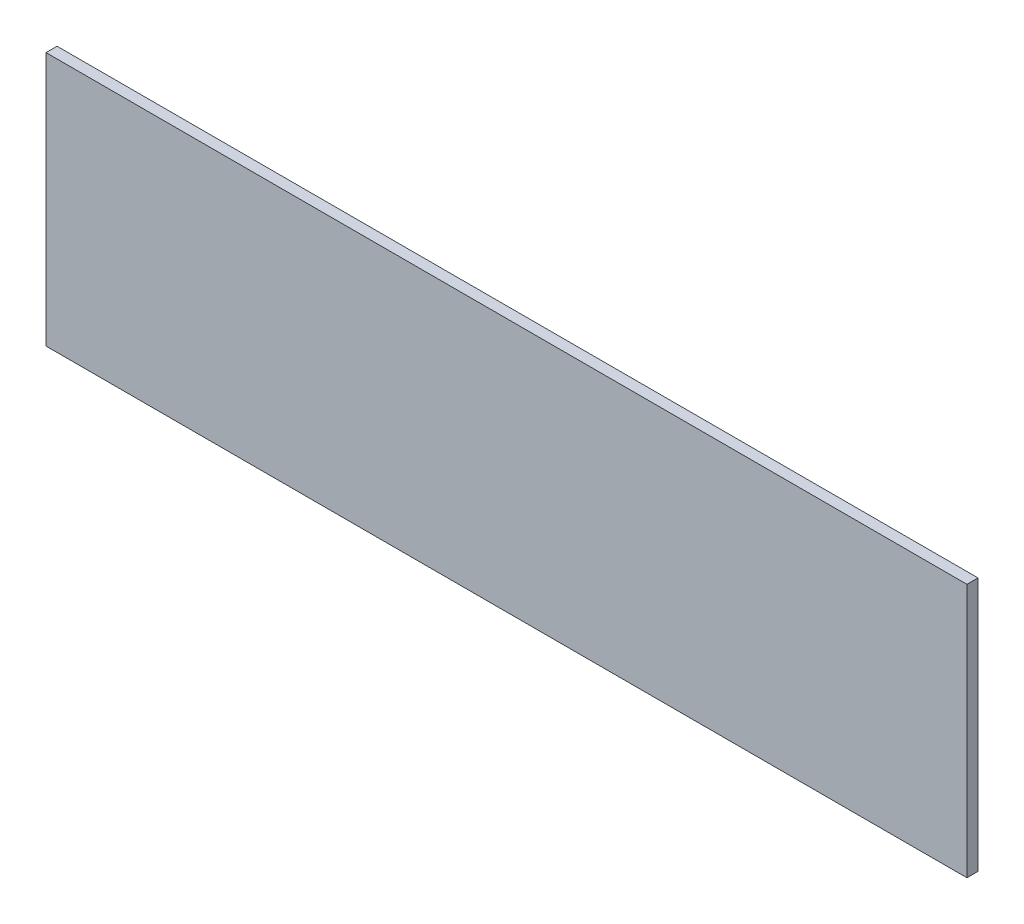
SolidWorks part; units mm, degrees
material "Pine"
ref_plane "Front Plane" through (0, 0, 0) normal (0, 0, 1) x (1, 0, 0)
ref_plane "Top Plane" through (0, 0, 0) normal (0, 1, 0) x (1, 0, 0)
ref_plane "Right Plane" through (0, 0, 0) normal (1, 0, 0) x (0, 0, -1)
sketch "Sketch1" plane through (0, 0, 0) normal (0, 0, 1) x (1, 0, 0)
  line L6 (0, 0) -> (1000, 0)
  line L10 (0, 0) -> (0, 276)
  line L11 (0, 276) -> (1000, 276)
  line L12 (1000, 0) -> (1000, 276)
  dimension "D3" = 276
  dimension "D1" = 1000
extrude "Boss-Extrude1" add sketch "Sketch1" along normal blind 12 contours L10 L11 L12 L6
equation "\"LENGTH\" = 1000mm"
equation "\"PLY\"= 12mm"
equation "\"D1@Sketch1\"=\"LENGTH\""
equation "\"D1@Boss-Extrude1\"=\"PLY\""
